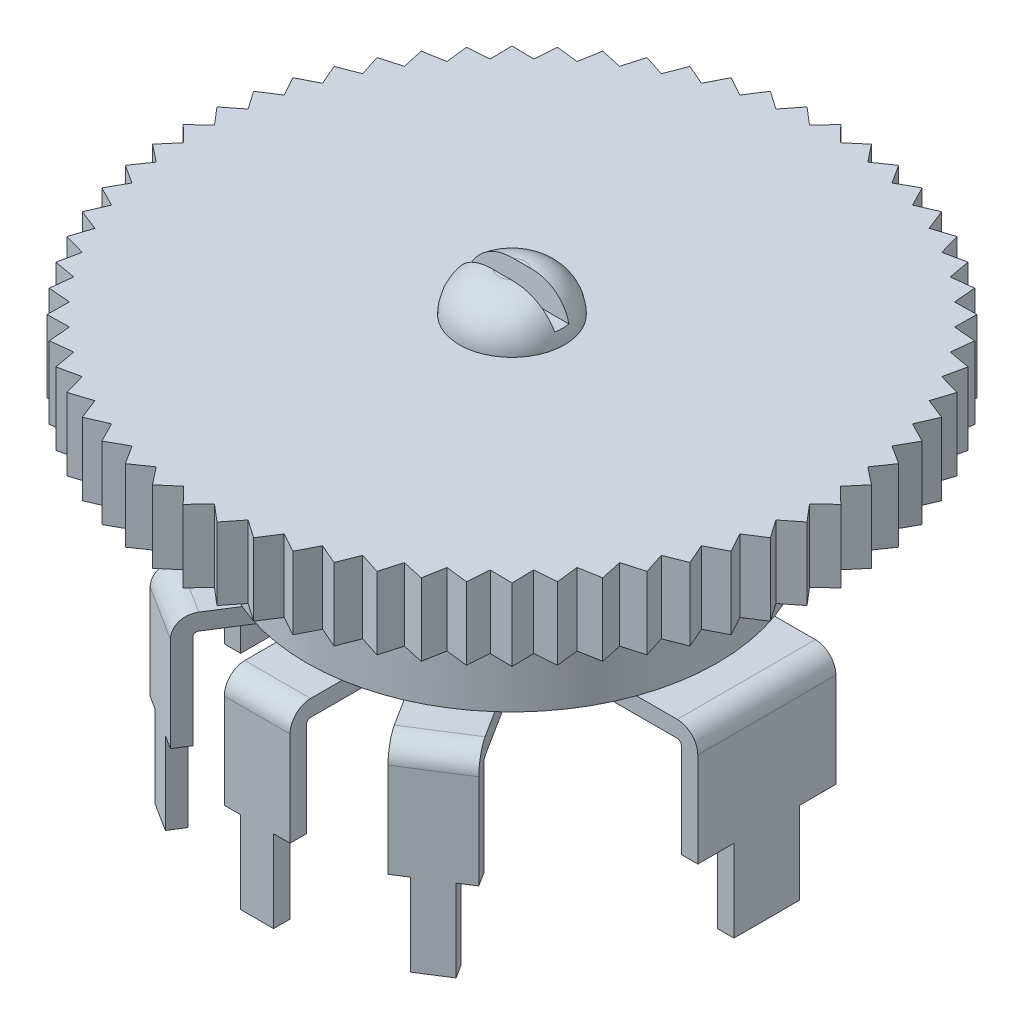
SolidWorks part; units mm, degrees
ref_plane "Front Plane" through (0, 0, 0) normal (0, 0, 1) x (1, 0, 0)
ref_plane "Top Plane" through (0, 0, 0) normal (0, 1, 0) x (1, 0, 0)
ref_plane "Right Plane" through (0, 0, 0) normal (1, 0, 0) x (0, 0, -1)
sketch "Sketch1" plane through (0, 0, 0) normal (0, 1, 0) x (1, 0, 0)
  line L0 (-7.25, 0) -> (7.25, 0) construction
  line L1 (7.25, 2.1) -> (7.75, 2.1)
  line L2 (7.25, 2.1) -> (7.25, -2.1)
  line L3 (7.25, -2.1) -> (7.75, -2.1)
  line L4 (7.75, 2.1) -> (7.75, -2.1)
  line L5 (-7.75, 2) -> (-7.25, 2)
  line L6 (-7.75, 2) -> (-7.75, -2)
  line L7 (-7.75, -2) -> (-7.25, -2)
  line L8 (-7.25, 2) -> (-7.25, -2)
  line L9 (0, 0) -> (0, -7.25) construction
  line L10 (-1, -7.25) -> (1, -7.25)
  line L11 (-1, -7.25) -> (-1, -7.75)
  line L12 (-1, -7.75) -> (1, -7.75)
  line L13 (1, -7.25) -> (1, -7.75)
  line L14 (0, 0) -> (-3.8847, -6.1214) construction
  line L15 (0, 0) -> (3.8847, -6.1214) construction
  line L16 (-4.997, -6.0077) -> (-3.3083, -7.0794)
  line L17 (-4.997, -6.0077) -> (-4.7291, -5.5856)
  line L18 (-3.3083, -7.0794) -> (-3.0404, -6.6572)
  line L19 (-4.7291, -5.5856) -> (-3.0404, -6.6572)
  line L20 (3.3083, -7.0794) -> (4.997, -6.0077)
  line L21 (3.3083, -7.0794) -> (3.0404, -6.6572)
  line L22 (4.997, -6.0077) -> (4.7291, -5.5856)
  line L23 (3.0404, -6.6572) -> (4.7291, -5.5856)
  line L24 (-4.863, -5.7966) -> (-3.1744, -6.8683) construction
  line L25 (3.1744, -6.8683) -> (4.863, -5.7966) construction
  point P11 (-7.5, 2)
  point P12 (7.5, 2.1)
  point P19 (1, -7.5)
  dimension "D1" = 4.2
  dimension "D2" = 4
  dimension "D3" = 0.5
  dimension "D4" = 15
  dimension "D5" = 0.5
  dimension "D6" = 2
  dimension "D7" = 7.5
  dimension "D8" = 32.4
  dimension "D9" = 32.4
  dimension "D10" = 7.5
  dimension "D11" = 7.5
extrude "Boss-Extrude1" add sketch "Sketch1" along normal blind 3.5
sketch "Sketch2" plane through (0, 0, 0) normal (0, -1, 0) x (1, 0, 0)
  line L0 (7.25, -2.1) -> (7.25, 2.1) construction
  line L1 (7.25, 1) -> (7.75, 1)
  line L2 (7.25, 1) -> (7.25, -1)
  line L3 (7.25, -1) -> (7.75, -1)
  line L4 (7.75, 1) -> (7.75, -1)
  line L5 (7.75, 2.1) -> (7.75, -2.1) construction
  line L6 (-7.75, -2) -> (-7.75, 2) construction
  line L7 (-7.75, 1) -> (-7.25, 1)
  line L8 (-7.75, 1) -> (-7.75, -1)
  line L9 (-7.75, -1) -> (-7.25, -1)
  line L10 (-7.25, 1) -> (-7.25, -1)
  line L11 (-7.25, 2) -> (-7.25, -2) construction
  line L12 (-1, 7.75) -> (1, 7.75) construction
  line L13 (-0.5, 7.75) -> (0.5, 7.75)
  line L14 (-0.5, 7.75) -> (-0.5, 7.25)
  line L15 (-0.5, 7.25) -> (0.5, 7.25)
  line L16 (0.5, 7.75) -> (0.5, 7.25)
  line L17 (1, 7.25) -> (-1, 7.25) construction
  line L18 (-4.5748, 6.2756) -> (-3.7305, 6.8115)
  line L19 (-4.5748, 6.2756) -> (-4.3069, 5.8535)
  line L20 (-3.7305, 6.8115) -> (-3.4626, 6.3893)
  line L21 (-4.3069, 5.8535) -> (-3.4626, 6.3893)
  line L22 (-4.997, 6.0077) -> (-3.3083, 7.0794) construction
  line L24 (3.4626, 6.3893) -> (4.3069, 5.8535)
  line L25 (3.4626, 6.3893) -> (3.7305, 6.8115)
  line L26 (4.3069, 5.8535) -> (4.5748, 6.2756)
  line L27 (3.7305, 6.8115) -> (4.5748, 6.2756)
  line L28 (4.7291, 5.5856) -> (3.0404, 6.6572) construction
  line L30 (3.3083, 7.0794) -> (4.997, 6.0077) construction
  line L31 (3.0404, 6.6572) -> (3.3083, 7.0794) construction
  line L32 (-3.3083, 7.0794) -> (-3.0404, 6.6572) construction
  line L33 (-3.0404, 6.6572) -> (-4.7291, 5.5856) construction
  line L34 (1, 7.75) -> (1, 7.25) construction
  line L35 (-7.25, 0) -> (0, 0) construction
  point P38 (3.1744, 6.8683)
  dimension "D1" = 1
  dimension "D2" = 0.5
  dimension "D3" = 0.5
  dimension "D4" = 2
  dimension "D5" = 0.5
extrude "Boss-Extrude2" add sketch "Sketch2" along normal blind 2.5
sketch "Sketch3" plane through (0, 3.5, 0) normal (0, 1, 0) x (1, 0, 0)
  line L0 (1, -7.75) -> (1, -7.25) construction
  line L1 (-1, -7.75) -> (1, -7.75)
  line L2 (-1, -7.75) -> (-1, -4.4)
  line L3 (3.3083, -7.0794) -> (4.997, -6.0077)
  line L4 (1, -7.75) -> (1, -4.4)
  line L5 (3.3083, -7.0794) -> (1.5133, -4.2509)
  line L6 (4.997, -6.0077) -> (3.202, -3.1792)
  line L7 (-7.75, 2) -> (-7.75, -2)
  line L8 (-4.997, -6.0077) -> (-3.3083, -7.0794)
  line L9 (-4.997, -6.0077) -> (-3.202, -3.1792)
  line L10 (-3.3083, -7.0794) -> (-1.5133, -4.2509)
  line L11 (-7.75, 2) -> (-4.125, 2)
  line L12 (-7.75, -2) -> (-4.125, -2)
  line L13 (-3.125, 1) -> (-3.125, -1)
  line L14 (7.75, -2.1) -> (7.75, 2.1)
  line L15 (7.75, -2.1) -> (4.125, -2.1)
  line L16 (7.75, 2.1) -> (4.125, 2.1)
  line L17 (3.125, -1.1) -> (3.125, 1.1)
  arc A0 (1, -4.4) -> (-1, -4.4) centre (0, -4.4) ccw
  arc A1 (3.202, -3.1792) -> (1.5133, -4.2509) centre (2.3576, -3.715) ccw
  arc A2 (-1.5133, -4.2509) -> (-3.202, -3.1792) centre (-2.3576, -3.715) ccw
  arc A3 (4.125, 2.1) -> (3.125, 1.1) centre (4.125, 1.1) ccw
  arc A4 (4.125, -2.1) -> (3.125, -1.1) centre (4.125, -1.1) cw
  arc A5 (-4.125, -2) -> (-3.125, -1) centre (-4.125, -1) ccw
  arc A6 (-4.125, 2) -> (-3.125, 1) centre (-4.125, 1) cw
  dimension "D3" = 1
  dimension "D1" = 3.35
  dimension "D2" = 4.625
extrude "Boss-Extrude3" add sketch "Sketch3" against normal blind 0.5
sketch "Sketch5" plane through (0, 3.5, 0) normal (0, 1, 0) x (1, 0, 0)
  circle A0 centre (0, 0) radius 6.25
  dimension "D1" = 12.5
extrude "Boss-Extrude4" add sketch "Sketch5" along normal offset from surface (3.7 mm away) 7.2 up to face at (-7.4375, 0, 1.5)
fillet "Fillet6" radius 0.625 5 edges at (7.75, 3.5, 0) (4.1527, 3.5, 6.5435) (0, 3.5, 7.75) (-4.1527, 3.5, 6.5435) (-7.75, 3.5, 0)
fillet "Fillet8" radius 0.125 5 edges at (7.25, 3, 0) (3.8847, 3, 6.1214) (0, 3, 7.25) (-3.8847, 3, 6.1214) (-7.25, 3, 0)
sketch "Sketch6" plane through (0, 7.2, 0) normal (0, 1, 0) x (1, 0, 0)
  line L0 (0, 0) -> (-2.4176, 2.4176) construction
  line L1 (0, 0) -> (0, 4.6138) construction
  line L2 (0.0112, -1.75) -> (-1.7134, 0.3562)
  line L5 (1.7134, -0.3562) -> (-0.0112, 1.75)
  line L6 (0.2319, -2.0196) -> (-0.2319, 2.0196) construction
  line L7 (-1.9341, 0.6258) -> (1.9341, -0.6258) construction
  arc A0 (-0.0112, 1.75) -> (-1.7134, 0.3562) centre (0, 0) ccw
  arc A1 (0.0112, -1.75) -> (1.7134, -0.3562) centre (0, 0) ccw
  dimension "D1" = 3.5
  dimension "D2" = 45
  dimension "D3" = 2.2
extrude "Boss-Extrude5" add sketch "Sketch6" along normal blind 0.9
sketch "Sketch8" plane through (0, 8.1, 0) normal (0, 1, 0) x (1, 0, 0)
  line L0 (0.9802, 9.9518) -> (1.398, 9.4243)
  line L1 (0, 10) -> (-0.4675, 9.5159)
  line L2 (0, 10) -> (0.4675, 9.5159)
  line L3 (0.9802, 9.9518) -> (0.4675, 9.5159)
  line L4 (1.9509, 9.8079) -> (2.315, 9.2419)
  line L5 (1.9509, 9.8079) -> (1.398, 9.4243)
  line L6 (2.9028, 9.5694) -> (3.2097, 8.9704)
  line L7 (2.9028, 9.5694) -> (2.315, 9.2419)
  line L8 (3.8268, 9.2388) -> (4.0735, 8.6126)
  line L9 (3.8268, 9.2388) -> (3.2097, 8.9704)
  line L10 (4.714, 8.8192) -> (4.8981, 8.1719)
  line L11 (4.714, 8.8192) -> (4.0735, 8.6126)
  line L12 (5.5557, 8.3147) -> (5.6755, 7.6525)
  line L13 (5.5557, 8.3147) -> (4.8981, 8.1719)
  line L14 (6.3439, 7.7301) -> (6.3982, 7.0593)
  line L15 (6.3439, 7.7301) -> (5.6755, 7.6525)
  line L16 (7.0711, 7.0711) -> (7.0593, 6.3982)
  line L17 (7.0711, 7.0711) -> (6.3982, 7.0593)
  line L18 (7.7301, 6.3439) -> (7.6525, 5.6755)
  line L19 (7.7301, 6.3439) -> (7.0593, 6.3982)
  line L20 (8.3147, 5.5557) -> (8.1719, 4.8981)
  line L21 (8.3147, 5.5557) -> (7.6525, 5.6755)
  line L22 (8.8192, 4.714) -> (8.6126, 4.0735)
  line L23 (8.8192, 4.714) -> (8.1719, 4.8981)
  line L24 (9.2388, 3.8268) -> (8.9704, 3.2097)
  line L25 (9.2388, 3.8268) -> (8.6126, 4.0735)
  line L26 (9.5694, 2.9028) -> (9.2419, 2.315)
  line L27 (9.5694, 2.9028) -> (8.9704, 3.2097)
  line L28 (9.8079, 1.9509) -> (9.4243, 1.398)
  line L29 (9.8079, 1.9509) -> (9.2419, 2.315)
  line L30 (9.9518, 0.9802) -> (9.5159, 0.4675)
  line L31 (9.9518, 0.9802) -> (9.4243, 1.398)
  line L32 (10, 0) -> (9.5159, -0.4675)
  line L33 (10, 0) -> (9.5159, 0.4675)
  line L34 (9.9518, -0.9802) -> (9.4243, -1.398)
  line L35 (9.9518, -0.9802) -> (9.5159, -0.4675)
  line L36 (9.8079, -1.9509) -> (9.2419, -2.315)
  line L37 (9.8079, -1.9509) -> (9.4243, -1.398)
  line L38 (9.5694, -2.9028) -> (8.9704, -3.2097)
  line L39 (9.5694, -2.9028) -> (9.2419, -2.315)
  line L40 (9.2388, -3.8268) -> (8.6126, -4.0735)
  line L41 (9.2388, -3.8268) -> (8.9704, -3.2097)
  line L42 (8.8192, -4.714) -> (8.1719, -4.8981)
  line L43 (8.8192, -4.714) -> (8.6126, -4.0735)
  line L44 (8.3147, -5.5557) -> (7.6525, -5.6755)
  line L45 (8.3147, -5.5557) -> (8.1719, -4.8981)
  line L46 (7.7301, -6.3439) -> (7.0593, -6.3982)
  line L47 (7.7301, -6.3439) -> (7.6525, -5.6755)
  line L48 (7.0711, -7.0711) -> (6.3982, -7.0593)
  line L49 (7.0711, -7.0711) -> (7.0593, -6.3982)
  line L50 (6.3439, -7.7301) -> (5.6755, -7.6525)
  line L51 (6.3439, -7.7301) -> (6.3982, -7.0593)
  line L52 (5.5557, -8.3147) -> (4.8981, -8.1719)
  line L53 (5.5557, -8.3147) -> (5.6755, -7.6525)
  line L54 (4.714, -8.8192) -> (4.0735, -8.6126)
  line L55 (4.714, -8.8192) -> (4.8981, -8.1719)
  line L56 (3.8268, -9.2388) -> (3.2097, -8.9704)
  line L57 (3.8268, -9.2388) -> (4.0735, -8.6126)
  line L58 (2.9028, -9.5694) -> (2.315, -9.2419)
  line L59 (2.9028, -9.5694) -> (3.2097, -8.9704)
  line L60 (1.9509, -9.8079) -> (1.398, -9.4243)
  line L61 (1.9509, -9.8079) -> (2.315, -9.2419)
  line L62 (0.9802, -9.9518) -> (0.4675, -9.5159)
  line L63 (0.9802, -9.9518) -> (1.398, -9.4243)
  line L64 (0, -10) -> (-0.4675, -9.5159)
  line L65 (0, -10) -> (0.4675, -9.5159)
  line L66 (-0.9802, -9.9518) -> (-1.398, -9.4243)
  line L67 (-0.9802, -9.9518) -> (-0.4675, -9.5159)
  line L68 (-1.9509, -9.8079) -> (-2.315, -9.2419)
  line L69 (-1.9509, -9.8079) -> (-1.398, -9.4243)
  line L70 (-2.9028, -9.5694) -> (-3.2097, -8.9704)
  line L71 (-2.9028, -9.5694) -> (-2.315, -9.2419)
  line L72 (-3.8268, -9.2388) -> (-4.0735, -8.6126)
  line L73 (-3.8268, -9.2388) -> (-3.2097, -8.9704)
  line L74 (-4.714, -8.8192) -> (-4.8981, -8.1719)
  line L75 (-4.714, -8.8192) -> (-4.0735, -8.6126)
  line L76 (-5.5557, -8.3147) -> (-5.6755, -7.6525)
  line L77 (-5.5557, -8.3147) -> (-4.8981, -8.1719)
  line L78 (-6.3439, -7.7301) -> (-6.3982, -7.0593)
  line L79 (-6.3439, -7.7301) -> (-5.6755, -7.6525)
  line L80 (-7.0711, -7.0711) -> (-7.0593, -6.3982)
  line L81 (-7.0711, -7.0711) -> (-6.3982, -7.0593)
  line L82 (-7.7301, -6.3439) -> (-7.6525, -5.6755)
  line L83 (-7.7301, -6.3439) -> (-7.0593, -6.3982)
  line L84 (-8.3147, -5.5557) -> (-8.1719, -4.8981)
  line L85 (-8.3147, -5.5557) -> (-7.6525, -5.6755)
  line L86 (-8.8192, -4.714) -> (-8.6126, -4.0735)
  line L87 (-8.8192, -4.714) -> (-8.1719, -4.8981)
  line L88 (-9.2388, -3.8268) -> (-8.9704, -3.2097)
  line L89 (-9.2388, -3.8268) -> (-8.6126, -4.0735)
  line L90 (-9.5694, -2.9028) -> (-9.2419, -2.315)
  line L91 (-9.5694, -2.9028) -> (-8.9704, -3.2097)
  line L92 (-9.8079, -1.9509) -> (-9.4243, -1.398)
  line L93 (-9.8079, -1.9509) -> (-9.2419, -2.315)
  line L94 (-9.9518, -0.9802) -> (-9.5159, -0.4675)
  line L95 (-9.9518, -0.9802) -> (-9.4243, -1.398)
  line L96 (-10, 0) -> (-9.5159, 0.4675)
  line L97 (-10, 0) -> (-9.5159, -0.4675)
  line L98 (-9.9518, 0.9802) -> (-9.4243, 1.398)
  line L99 (-9.9518, 0.9802) -> (-9.5159, 0.4675)
  line L100 (-9.8079, 1.9509) -> (-9.2419, 2.315)
  line L101 (-9.8079, 1.9509) -> (-9.4243, 1.398)
  line L102 (-9.5694, 2.9028) -> (-8.9704, 3.2097)
  line L103 (-9.5694, 2.9028) -> (-9.2419, 2.315)
  line L104 (-9.2388, 3.8268) -> (-8.6126, 4.0735)
  line L105 (-9.2388, 3.8268) -> (-8.9704, 3.2097)
  line L106 (-8.8192, 4.714) -> (-8.1719, 4.8981)
  line L107 (-8.8192, 4.714) -> (-8.6126, 4.0735)
  line L108 (-8.3147, 5.5557) -> (-7.6525, 5.6755)
  line L109 (-8.3147, 5.5557) -> (-8.1719, 4.8981)
  line L110 (-7.7301, 6.3439) -> (-7.0593, 6.3982)
  line L111 (-7.7301, 6.3439) -> (-7.6525, 5.6755)
  line L112 (-7.0711, 7.0711) -> (-6.3982, 7.0593)
  line L113 (-7.0711, 7.0711) -> (-7.0593, 6.3982)
  line L114 (-6.3439, 7.7301) -> (-5.6755, 7.6525)
  line L115 (-6.3439, 7.7301) -> (-6.3982, 7.0593)
  line L116 (-5.5557, 8.3147) -> (-4.8981, 8.1719)
  line L117 (-5.5557, 8.3147) -> (-5.6755, 7.6525)
  line L118 (-4.714, 8.8192) -> (-4.0735, 8.6126)
  line L119 (-4.714, 8.8192) -> (-4.8981, 8.1719)
  line L120 (-3.8268, 9.2388) -> (-3.2097, 8.9704)
  line L121 (-3.8268, 9.2388) -> (-4.0735, 8.6126)
  line L122 (-2.9028, 9.5694) -> (-2.315, 9.2419)
  line L123 (-2.9028, 9.5694) -> (-3.2097, 8.9704)
  line L124 (-1.9509, 9.8079) -> (-1.398, 9.4243)
  line L125 (-1.9509, 9.8079) -> (-2.315, 9.2419)
  line L126 (-0.9802, 9.9518) -> (-0.4675, 9.5159)
  line L127 (-0.9802, 9.9518) -> (-1.398, 9.4243)
  circle A0 centre (0, 0) radius 10 construction
  dimension "D1" = 88
  dimension "D2" = 64
extrude "Boss-Extrude6" add sketch "Sketch8" against normal blind 0.75 and the other way blind 1.45
sketch "Sketch9" plane through (0, 9.55, 0) normal (0, 1, 0) x (1, 0, 0)
  circle A0 centre (0, 0) radius 1.6
  dimension "D1" = 3.2
extrude "Boss-Extrude7" add sketch "Sketch9" along normal blind 1.2
fillet "Fillet9" radius 1.2 1 edges at (0, 10.75, 1.6)
sketch "Sketch10" plane through (0, 10.75, 0) normal (0, 1, 0) x (1, 0, 0)
  line L1 (-2.1722, -0.3) -> (2.1722, -0.3)
  line L2 (-2.1722, -0.3) -> (-2.1722, 0.3)
  line L3 (-2.1722, 0.3) -> (2.1722, 0.3)
  line L4 (2.1722, -0.3) -> (2.1722, 0.3)
  line L5 (-2.1722, -0.3) -> (2.1722, 0.3) construction
  line L6 (-2.1722, 0.3) -> (2.1722, -0.3) construction
  point P0 (0, 0)
  point P6 (0, 0)
  dimension "D1" = 0.6
extrude "Cut-Extrude1" cut sketch "Sketch10" against normal blind 0.8 draft 6
sketch "Sketch11" plane through (0, 3, 0) normal (0, -1, 0) x (1, 0, 0)
  line L0 (-4.75, 0) -> (4.75, 0) construction
  circle A0 centre (4.75, 0) radius 0.625
  circle A1 centre (-4.75, 0) radius 0.625
  circle A2 centre (-2.3576, 3.715) radius 0.425
  circle A3 centre (0, 4.4) radius 0.425
  circle A4 centre (2.3576, 3.715) radius 0.425
  circle A5 centre (-2.3576, 3.715) radius 0.675
  circle A6 centre (0, 4.4) radius 0.675
  circle A7 centre (2.3576, 3.715) radius 0.675
  circle A8 centre (4.75, 0) radius 0.875
  circle A9 centre (-4.75, 0) radius 0.875
  dimension "D2" = 0.85
  dimension "D3" = 1.25
  dimension "D4" = 0.25
  dimension "D1" = 9.5
extrude "Boss-Extrude8" add sketch "Sketch11" along normal blind 0.25
fillet "Fillet10" radius 0.125 10 edges at (4.75, 2.75, -0.625) (4.75, 2.75, -0.875) (2.3576, 2.75, 3.29) (2.3576, 2.75, 3.04) (0, 2.75, 3.975) (0, 2.75, 3.725) (-2.3576, 2.75, 3.29) (-2.3576, 2.75, 3.04) (-4.75, 2.75, -0.625) (-4.75, 2.75, -0.875)
sketch "Sketch12" plane through (0, 3, 0) normal (0, -1, 0) x (1, 0, 0)
  circle A0 centre (-2.3576, 3.715) radius 0.425 construction
  circle A1 centre (-4.75, 0) radius 0.625
  circle A2 centre (-4.75, 0) radius 0.625
  circle A3 centre (0, 4.4) radius 0.425 construction
  circle A4 centre (2.3576, 3.715) radius 0.425 construction
  circle A5 centre (4.75, 0) radius 0.625 construction
  circle A6 centre (-2.3576, 3.715) radius 0.425
  circle A7 centre (0, 4.4) radius 0.425
  circle A8 centre (2.3576, 3.715) radius 0.425
  circle A9 centre (4.75, 0) radius 0.625
  dimension "D1" = 0
extrude "Cut-Extrude3" cut sketch "Sketch12" against normal blind 0.25
